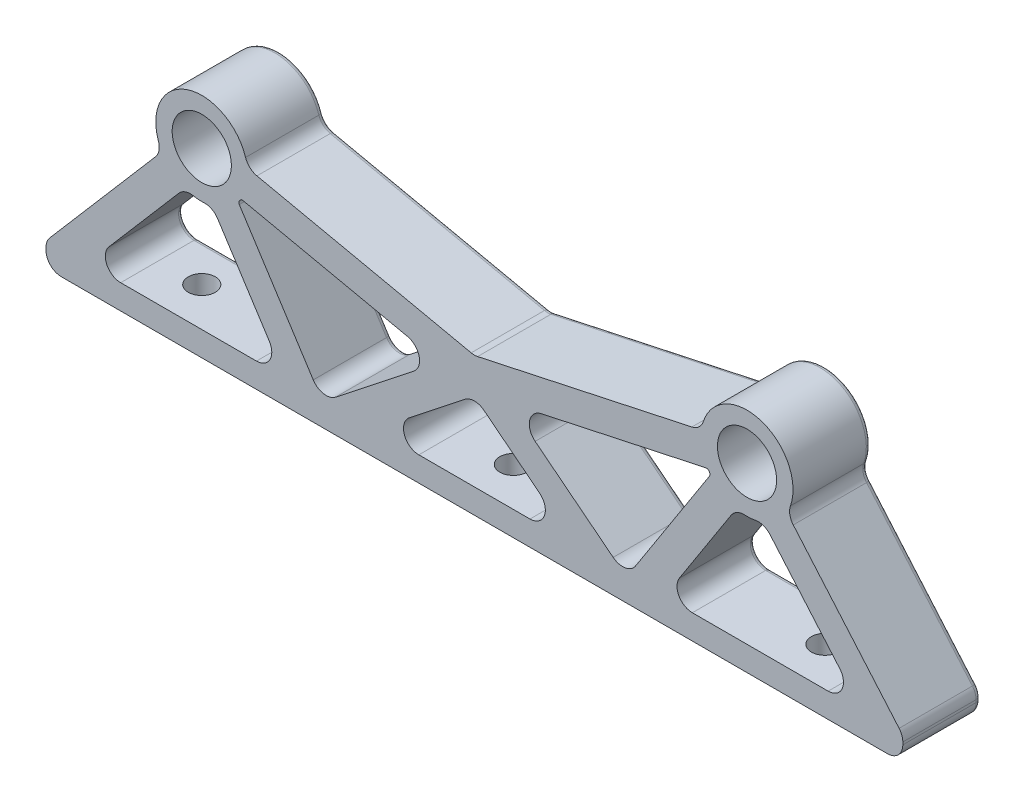
SolidWorks part; units mm, degrees
ref_plane "Front Plane" through (0, 0, 0) normal (0, 0, 1) x (1, 0, 0)
ref_plane "Top Plane" through (0, 0, 0) normal (0, 1, 0) x (1, 0, 0)
ref_plane "Right Plane" through (0, 0, 0) normal (1, 0, 0) x (0, 0, -1)
sketch "Sketch1" plane through (0, 0, 0) normal (0, 0, 1) x (1, 0, 0)
  line L0 (0, 0) -> (60.4965, 0) construction
  circle A0 centre (0, 0) radius 25.4 construction
  circle A1 centre (44.45, 35.921) radius 31.75 construction
  circle A2 centre (133.35, 35.921) radius 31.75 construction
  circle A3 centre (177.8, 0) radius 25.4 construction
  circle A4 centre (222.25, 35.921) radius 31.75 construction
  circle A5 centre (311.15, 35.921) radius 31.75 construction
  circle A6 centre (355.6, 0) radius 25.4 construction
  circle A7 centre (0, 0) radius 50.8 construction
  circle A8 centre (355.6, 0) radius 50.8 construction
  circle A9 centre (177.8, 0) radius 50.8 construction
  circle A10 centre (88.9, 35.921) radius 12.7 construction
  circle A11 centre (266.7, 35.921) radius 12.7 construction
  point P20 (-50.8, 0)
  point P21 (406.4, 0)
  dimension "D1" = 50.8
  dimension "D2" = 63.5
  dimension "D4" = 101.6
  dimension "D5" = 25.4
  dimension "D6" = 25.4
  dimension "D3" = 355.6
  dimension "D7" = 177.8
  dimension "D8" = 177.8
  dimension "D9" = 457.2
  dimension "D10" = 44.45
sketch "Sketch2" plane through (0, 0, 0) normal (0, 0, 1) x (1, 0, 0)
  line L0 (-200000, 0) -> (200060.4965, 0) construction
  line L1 (-44.45, 6.35) -> (400.05, 6.35) construction
  line L2 (-44.45, 6.35) -> (-44.45, -19.05) construction
  line L3 (-44.45, -19.05) -> (400.05, -19.05) construction
  line L4 (400.05, 6.35) -> (400.05, -19.05) construction
  circle A0 centre (-38.1, 0) radius 2.25 construction
  circle A2 centre (-31.75, -6.35) radius 2.25 construction
  circle A3 centre (-25.4, 0) radius 2.25 construction
  circle A4 centre (-12.7, 0) radius 2.25 construction
  circle A5 centre (0, 0) radius 2.25 construction
  circle A6 centre (12.7, 0) radius 2.25 construction
  circle A7 centre (25.4, 0) radius 2.25 construction
  circle A8 centre (38.1, 0) radius 2.25 construction
  circle A9 centre (50.8, 0) radius 2.25 construction
  circle A10 centre (63.5, 0) radius 2.25 construction
  circle A11 centre (76.2, 0) radius 2.25 construction
  circle A12 centre (88.9, 0) radius 2.25 construction
  circle A13 centre (101.6, 0) radius 2.25 construction
  circle A14 centre (114.3, 0) radius 2.25 construction
  circle A15 centre (127, 0) radius 2.25 construction
  circle A16 centre (139.7, 0) radius 2.25 construction
  circle A17 centre (152.4, 0) radius 2.25 construction
  circle A18 centre (165.1, 0) radius 2.25 construction
  circle A19 centre (177.8, 0) radius 2.25 construction
  circle A20 centre (190.5, 0) radius 2.25 construction
  circle A21 centre (203.2, 0) radius 2.25 construction
  circle A22 centre (215.9, 0) radius 2.25 construction
  circle A23 centre (228.6, 0) radius 2.25 construction
  circle A24 centre (241.3, 0) radius 2.25 construction
  circle A25 centre (254, 0) radius 2.25 construction
  circle A26 centre (266.7, 0) radius 2.25 construction
  circle A27 centre (279.4, 0) radius 2.25 construction
  circle A28 centre (292.1, 0) radius 2.25 construction
  circle A29 centre (304.8, 0) radius 2.25 construction
  circle A30 centre (317.5, 0) radius 2.25 construction
  circle A31 centre (330.2, 0) radius 2.25 construction
  circle A32 centre (342.9, 0) radius 2.25 construction
  circle A33 centre (355.6, 0) radius 2.25 construction
  circle A34 centre (368.3, 0) radius 2.25 construction
  circle A35 centre (381, 0) radius 2.25 construction
  circle A36 centre (393.7, 0) radius 2.25 construction
  circle A37 centre (-25.4, -12.7) radius 2.25 construction
  circle A38 centre (-12.7, -12.7) radius 2.25 construction
  circle A39 centre (0, -12.7) radius 2.25 construction
  circle A40 centre (12.7, -12.7) radius 2.25 construction
  circle A41 centre (25.4, -12.7) radius 2.25 construction
  circle A42 centre (38.1, -12.7) radius 2.25 construction
  circle A43 centre (50.8, -12.7) radius 2.25 construction
  circle A44 centre (63.5, -12.7) radius 2.25 construction
  circle A45 centre (76.2, -12.7) radius 2.25 construction
  circle A46 centre (88.9, -12.7) radius 2.25 construction
  circle A47 centre (101.6, -12.7) radius 2.25 construction
  circle A48 centre (114.3, -12.7) radius 2.25 construction
  circle A49 centre (127, -12.7) radius 2.25 construction
  circle A50 centre (139.7, -12.7) radius 2.25 construction
  circle A51 centre (152.4, -12.7) radius 2.25 construction
  circle A52 centre (165.1, -12.7) radius 2.25 construction
  circle A53 centre (177.8, -12.7) radius 2.25 construction
  circle A54 centre (190.5, -12.7) radius 2.25 construction
  circle A55 centre (203.2, -12.7) radius 2.25 construction
  circle A56 centre (215.9, -12.7) radius 2.25 construction
  circle A57 centre (228.6, -12.7) radius 2.25 construction
  circle A58 centre (241.3, -12.7) radius 2.25 construction
  circle A59 centre (254, -12.7) radius 2.25 construction
  circle A60 centre (266.7, -12.7) radius 2.25 construction
  circle A61 centre (279.4, -12.7) radius 2.25 construction
  circle A62 centre (292.1, -12.7) radius 2.25 construction
  circle A63 centre (304.8, -12.7) radius 2.25 construction
  circle A64 centre (317.5, -12.7) radius 2.25 construction
  circle A65 centre (330.2, -12.7) radius 2.25 construction
  circle A66 centre (342.9, -12.7) radius 2.25 construction
  circle A67 centre (355.6, -12.7) radius 2.25 construction
  circle A68 centre (368.3, -12.7) radius 2.25 construction
  circle A69 centre (381, -12.7) radius 2.25 construction
  circle A70 centre (393.7, -12.7) radius 2.25 construction
  circle A71 centre (-38.1, -12.7) radius 2.25 construction
  circle A72 centre (-19.05, -6.35) radius 2.25 construction
  circle A73 centre (-6.35, -6.35) radius 2.25 construction
  circle A74 centre (6.35, -6.35) radius 2.25 construction
  circle A75 centre (19.05, -6.35) radius 2.25 construction
  circle A76 centre (31.75, -6.35) radius 2.25 construction
  circle A77 centre (44.45, -6.35) radius 2.25 construction
  circle A78 centre (57.15, -6.35) radius 2.25 construction
  circle A79 centre (69.85, -6.35) radius 2.25 construction
  circle A80 centre (82.55, -6.35) radius 2.25 construction
  circle A81 centre (95.25, -6.35) radius 2.25 construction
  circle A82 centre (107.95, -6.35) radius 2.25 construction
  circle A83 centre (120.65, -6.35) radius 2.25 construction
  circle A84 centre (133.35, -6.35) radius 2.25 construction
  circle A85 centre (146.05, -6.35) radius 2.25 construction
  circle A86 centre (158.75, -6.35) radius 2.25 construction
  circle A87 centre (171.45, -6.35) radius 2.25 construction
  circle A88 centre (184.15, -6.35) radius 2.25 construction
  circle A89 centre (196.85, -6.35) radius 2.25 construction
  circle A90 centre (209.55, -6.35) radius 2.25 construction
  circle A91 centre (222.25, -6.35) radius 2.25 construction
  circle A92 centre (234.95, -6.35) radius 2.25 construction
  circle A93 centre (247.65, -6.35) radius 2.25 construction
  circle A94 centre (260.35, -6.35) radius 2.25 construction
  circle A95 centre (273.05, -6.35) radius 2.25 construction
  circle A96 centre (285.75, -6.35) radius 2.25 construction
  circle A97 centre (298.45, -6.35) radius 2.25 construction
  circle A98 centre (311.15, -6.35) radius 2.25 construction
  circle A99 centre (323.85, -6.35) radius 2.25 construction
  circle A100 centre (336.55, -6.35) radius 2.25 construction
  circle A101 centre (349.25, -6.35) radius 2.25 construction
  circle A102 centre (361.95, -6.35) radius 2.25 construction
  circle A103 centre (374.65, -6.35) radius 2.25 construction
  circle A104 centre (387.35, -6.35) radius 2.25 construction
  dimension "D5" = 4.5
  dimension "D1" = 25.4
  dimension "D2" = 444.5
  dimension "D3" = 6.35
  dimension "D4" = 44.45
  dimension "D6" = 6.35
  dimension "D7" = 6.35
  dimension "D8" = 6.35
  dimension "D12" = 12.7
  dimension "D9" = 35
  dimension "D10" = 2
  dimension "D11" = 34
sketch "Sketch3" plane through (0, 0, 0) normal (0, 0, 1) x (1, 0, 0)
  line L0 (44.45, 35.921) -> (88.9, 26.35) construction
  line L1 (88.9, 26.35) -> (133.35, 35.921) construction
  line L2 (44.45, 35.921) -> (19.05, 6.35) construction
  line L3 (-44.45, 6.35) -> (400.05, 6.35) construction
  line L4 (19.05, 6.35) -> (158.75, 6.35) construction
  line L5 (158.75, 6.35) -> (133.35, 35.921) construction
  line L6 (44.45, 35.921) -> (63.5, 6.35) construction
  line L7 (63.5, 6.35) -> (88.9, 26.35) construction
  line L8 (88.9, 26.35) -> (114.3, 6.35) construction
  line L9 (114.3, 6.35) -> (133.35, 35.921) construction
  line L10 (19.05, 6.35) -> (158.75, 6.35)
  line L11 (158.75, 6.35) -> (158.75, 10.1868)
  line L12 (158.75, 10.1868) -> (139.8538, 32.186)
  line L13 (88.9, 28.9073) -> (125.9111, 36.8766)
  line L14 (126.9636, 31.9886) -> (94.6237, 25.0251)
  line L15 (152.0186, 10.35) -> (119.8507, 10.35)
  line L16 (119.8507, 10.35) -> (131.6222, 28.6228)
  line L17 (152.0186, 10.35) -> (136.0609, 28.9281)
  line L18 (113.687, 10.0147) -> (127.4189, 31.3306)
  line L19 (113.687, 10.0147) -> (94.6237, 25.0251)
  line L20 (105.1789, 10.35) -> (72.6211, 10.35)
  line L21 (72.6211, 10.35) -> (88.9, 23.168)
  line L22 (105.1789, 10.35) -> (88.9, 23.168)
  line L24 (50.8364, 31.9886) -> (83.1763, 25.0251)
  line L26 (25.7814, 10.35) -> (57.9493, 10.35)
  line L27 (57.9493, 10.35) -> (46.1778, 28.6228)
  line L28 (25.7814, 10.35) -> (41.7391, 28.9281)
  line L29 (19.05, 6.35) -> (19.05, 10.1868)
  line L30 (19.05, 10.1868) -> (37.9462, 32.186)
  line L31 (51.8889, 36.8766) -> (88.9, 28.9073)
  line L32 (64.113, 10.0147) -> (50.3811, 31.3306)
  line L33 (64.113, 10.0147) -> (83.1763, 25.0251)
  circle A0 centre (44.45, 35.921) radius 4.826
  circle A2 centre (133.35, 35.921) radius 4.826
  circle A3 centre (44.45, 35.921) radius 7.5
  circle A5 centre (133.35, 35.921) radius 7.5
  circle A6 centre (44.45, 35.921) radius 2.5
  circle A7 centre (133.35, 35.921) radius 2.5
  dimension "D1" = 9.652
  dimension "D2" = 15
  dimension "D3" = 5
  dimension "D20" = 5
  dimension "Thickness" = 5
  dimension "D4" = 2.5
  dimension "D5" = 2.5
  dimension "D6" = 5
  dimension "D7" = 2.5
  dimension "D8" = 5
  dimension "D9" = 2.5
  dimension "D10" = 5
  dimension "D11" = 5
  dimension "D12" = 2.5
  dimension "D13" = 4
  dimension "D14" = 2.5
  dimension "D15" = 5
  dimension "D16" = 5
  dimension "D17" = 5
  dimension "D18" = 2.5
  dimension "D19" = 20
extrude "Boss-Extrude1" add sketch "Sketch3" along normal blind 12.7 contours A5 L13 L31 A3 L24 L33 L32 L27 L26 L28 L30 L29 L10 L11 L12 L17 L15 L16 L18 L19 L14 L22 L20 L21 | A3 A0 | A5 A2 region at (20.48, 8.2684, 0) region at (42.1262, 42.8285, 0) region at (138.0986, 30.3926, 0)
fillet "Fillet1" radius 2.5 24 edges at (158.75, 6.35, 6.35) (158.75, 10.1868, 6.35) (19.05, 6.35, 6.35) (19.05, 10.1868, 6.35) (139.8538, 32.186, 6.35) (125.9111, 36.8766, 6.35) (51.8889, 36.8766, 6.35) (152.0186, 10.35, 6.35) (136.0609, 28.9281, 6.35) (131.6222, 28.6228, 6.35) (119.8507, 10.35, 6.35) (113.687, 10.0147, 6.35) (105.1789, 10.35, 6.35) (25.7814, 10.35, 6.35) (41.7391, 28.9281, 6.35) (46.1778, 28.6228, 6.35) (57.9493, 10.35, 6.35) (72.6211, 10.35, 6.35) (64.113, 10.0147, 6.35) (37.9462, 32.186, 6.35) (88.9, 23.168, 6.35) (94.6237, 25.0251, 6.35) (83.1763, 25.0251, 6.35) (88.9, 28.9073, 6.35)
sketch "Sketch4" plane through (0, 6.35, 0) normal (0, -1, 0) x (1, 0, 0)
  line L0 (21.55, 12.7) -> (21.55, 0) construction
  circle A0 centre (38.1, 6.35) radius 2.2
  circle A1 centre (88.9, 6.35) radius 2.2
  circle A2 centre (139.7, 6.35) radius 2.2
  point P0 (139.7, 0)
  point P2 (88.9, 0)
  point P4 (38.1, 0)
  point P15 (21.55, 6.35)
  dimension "D1" = 4.4
extrude "Cut-Extrude1" cut sketch "Sketch4" against normal up to next
extrude "Boss-Extrude2" add sketch "Sketch3<3>" along normal blind 3.175 contours A0 | A2 region at (39.7605, 35.921, 0) region at (128.6605, 35.921, 0)
sketch "Sketch3<3>" plane through (0, 0, 0) normal (0, 0, 1) x (1, 0, 0) same geometry as "Sketch3"
fillet "Fillet4" radius 0.5 4 edges at (127.4189, 31.3306, 6.35) (126.9636, 31.9886, 6.35) (50.8364, 31.9886, 6.35) (50.3811, 31.3306, 6.35)
fillet "Fillet2" radius 0.75 58 edges at (135.85, 35.921, 0) (46.95, 35.921, 0) (77.475, 12.0316, 0) (82.822, 18.3822, 0) (88.9, 22.486, 0) (94.978, 18.3822, 0) (100.325, 12.0316, 0) (88.9, 10.35, 0) (136.0279, 28.4526, 0) (142.7842, 21.1008, 0) (148.8474, 11.8065, 0) (135.5053, 10.35, 0) (122.2402, 11.6531, 0) (126.5475, 20.7453, 0) (131.7201, 28.1562, 0) (133.8647, 28.4387, 0) (46.0799, 28.1562, 0) (51.2525, 20.7453, 0) (55.5598, 11.6531, 0) (42.2947, 10.35, 0) (28.9526, 11.8065, 0) (35.0158, 21.1008, 0) (41.7721, 28.4526, 0) (43.9353, 28.4387, 0) (64.5763, 29.0301, 0) (79.8882, 24.264, 0) (72.6359, 16.7256, 0) (64.3136, 11.2136, 0) (56.5962, 21.6829, 0) (158.5943, 10.1291, 0) (149.5179, 20.935, 0) (140.3289, 32.1469, 0) (135.7414, 43.0295, 0) (125.509, 37.1326, 0) (106.8919, 32.7813, 0) (88.9, 28.9646, 0) (70.9081, 32.7813, 0) (52.291, 37.1326, 0) (42.0586, 43.0295, 0) (37.4711, 32.1469, 0) (28.2821, 20.935, 0) (19.2057, 10.1291, 0) (19.05, 9.0553, 0) (19.7822, 7.0822, 0) (88.9, 6.35, 0) (158.0178, 7.0822, 0) (158.75, 9.0553, 0) (121.2038, 21.6829, 0) (113.4864, 11.2136, 0) (105.1641, 16.7256, 0) (97.9118, 24.264, 0) (113.2237, 29.0301, 0) (50.4884, 31.3217, 0) (50.6175, 31.6535, 0) (50.8826, 31.8913, 0) (127.3116, 31.3217, 0) (126.9174, 31.8913, 0) (127.1825, 31.6535, 0)
